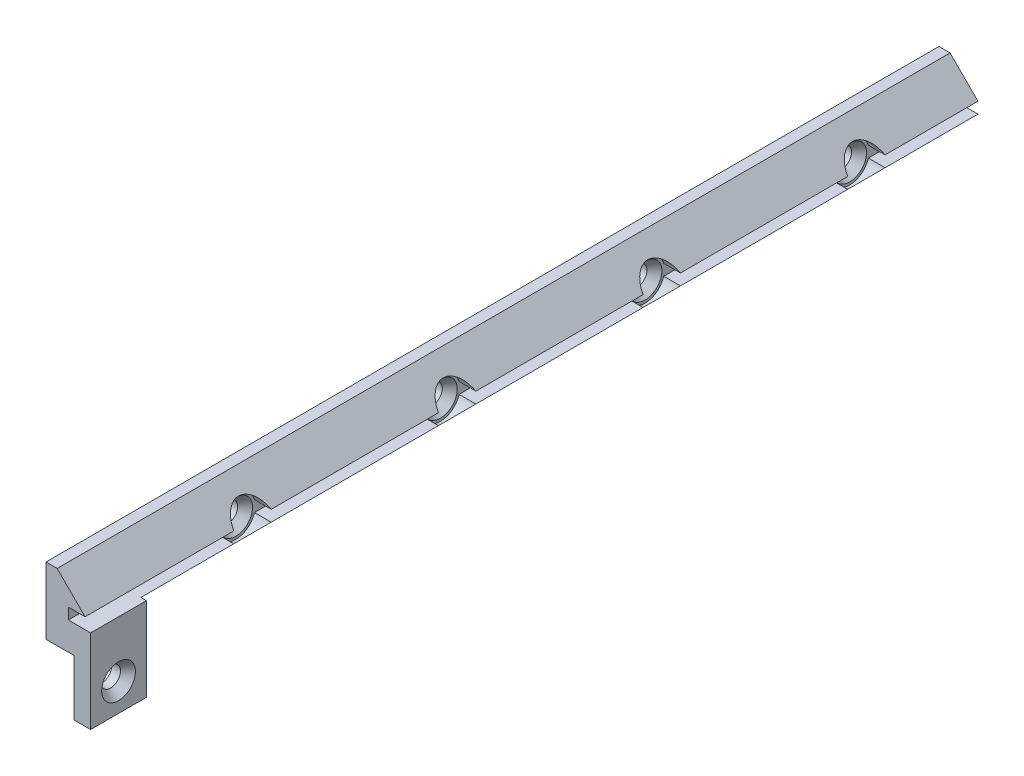
SolidWorks part; units mm, degrees
ref_plane "Front Plane" through (0, 0, 0) normal (0, 0, 1) x (1, 0, 0)
ref_plane "Top Plane" through (0, 0, 0) normal (0, 1, 0) x (1, 0, 0)
ref_plane "Right Plane" through (0, 0, 0) normal (1, 0, 0) x (0, 0, -1)
sketch "Sketch1" plane through (0, 0, 0) normal (0, 0, 1) x (1, 0, 0)
  line L0 (-2, 0) -> (0, 0) construction
  line L1 (-2, -3) -> (2, -3)
  line L2 (-2, -3) -> (-2, 3)
  line L3 (-2, 3) -> (2, 3)
  line L4 (2, -3) -> (2, -0.5)
  line L5 (-2, -3) -> (2, 3) construction
  line L6 (-2, 3) -> (2, -3) construction
  line L7 (2, 0.5) -> (0, 0.5)
  line L9 (2, -0.5) -> (0, -0.5)
  line L10 (0, 0.5) -> (0, -0.5)
  line L11 (2, 0.5) -> (2, 3)
  point P0 (0, 0)
  dimension "D1" = 1
  dimension "D2" = 6
  dimension "D3" = 2
  dimension "D4" = 4
extrude "Boss-Extrude1" add sketch "Sketch1" along normal blind 75
sketch "Sketch5" plane through (2, 0, 0) normal (1, 0, 0) x (0, 0, -1)
  line L1 (-75, 0) -> (0, 0) construction
  line L4 (-75, -0.5) -> (-75, 0.5) construction
  circle A0 centre (-65, 0) radius 1.75
  circle A1 centre (-46.6667, 0) radius 1.75
  circle A2 centre (-28.3333, 0) radius 1.75
  circle A3 centre (-10, 0) radius 1.75
  point P6 (-65, 0)
  dimension "D1" = 3.5
  dimension "D2" = 10
  dimension "D3" = 10
  dimension "D5" = 4
extrude "Cut-Extrude1" cut sketch "Sketch5" against normal up to surface (2 mm away) up to face at (0, 0, 37.5)
hole_wizard "CSK for #0 Flat Head Machine Screw2" positions "Sketch4" profile "Sketch2" countersink size "#0" standard "ANSI Inch"
sketch "Sketch4" plane through (0, 0, 0) normal (1, 0, 0) x (0, 0, -1)
  arc A0 (-63.3229, 0.5) -> (-66.6771, 0.5) centre (-65, 0) ccw construction
  arc A3 (-44.9896, 0.5) -> (-48.3437, 0.5) centre (-46.6667, 0) ccw construction
  arc A4 (-8.323, 0.5) -> (-11.6771, 0.5) centre (-10, 0) ccw construction
  point P0 (-65, 0)
  point P2 (-10, 0)
  point P4 (-46.6667, 0)
  point P25 (-28.3333, 0)
sketch "Sketch2" plane through (0, 0, 65) normal (0, 1, 0) x (0, 0, -1)
  line L0 (0, 0) -> (0, 3.8362)
  line L1 (0, 3.8362) -> (0.889, 3.302)
  line L2 (0.889, 3.302) -> (0.889, 0.7159)
  line L3 (0.889, 0.7159) -> (1.5113, 0)
  line L5 (1.5113, 0) -> (0, 0)
  line L6 (-0.889, 0.7159) -> (-1.5113, 0) construction
  line L10 (0, 3.8362) -> (-0.889, 3.302) construction
  line L11 (0, -6.35) -> (0, 107.95) construction
  dimension "Hole Dia." = 1.778
  dimension "Hole Depth" = 3.302
  dimension "Near C'Sink Dia." = 3.0226
  dimension "Near C'Sink Angle" = 82
  dimension "Drill Angle" = 118
chamfer "Chamfer1" distance 3 angle 45 2 edges at (2, -3, 37.5) (2, 3, 37.5)
sketch "Sketch6" plane through (0, 0, 75) normal (0, 0, 1) x (1, 0, 0)
  line L0 (-2, -3) -> (-1, -3) construction
  line L1 (2, 3) -> (2, 0.5)
  line L2 (-2, 3) -> (-2, -3)
  line L3 (-2, -3) -> (2, -3)
  line L5 (-2, 3) -> (-2, -3) construction
  line L6 (2, -0.5) -> (2, -3)
  line L7 (2, 0.5) -> (0, 0.5)
  line L8 (0, 0.5) -> (1.5, 0.5) construction
  line L9 (2, -0.5) -> (0, -0.5)
  line L10 (0, 0.5) -> (0, -0.5)
  line L11 (-2, 3) -> (2, 3)
  line L12 (-1, 3) -> (-2, 3) construction
  line L13 (2, -3) -> (0.5, -3)
  line L14 (2, -3) -> (2, -8)
  line L15 (2, -8) -> (0.5, -8)
  line L16 (0.5, -3) -> (0.5, -8)
  line M4 (-2, -3) -> (-1, -3)
  line M6 (1.5, -0.5) -> (0, -0.5)
  line M7 (0, -0.5) -> (0, 0.5)
  line M8 (0, 0.5) -> (1.5, 0.5)
  line M10 (-1, 3) -> (-2, 3)
  line M11 (-2, 3) -> (-2, -3)
  line M21 (-1, -3) -> (1.5, -0.5)
  line M22 (1.5, 0.5) -> (-1, 3)
  dimension "D1" = 4
  dimension "D2" = 2.5
  dimension "D3" = 5
  dimension "D4" = 1.5
extrude "Boss-Extrude2" add sketch "Sketch6" along normal blind 5 contours M11 M4 M21 M6 M7 M8 M22 M10 | L6 L9 L3 M21 | L3 L16 L15 L14 region at (-0.7956, 0, 75) region at (0.9762, -2.0476, 75) region at (1.25, -5.5, 75)
hole_wizard "CSK for #0 Flat Head Machine Screw1" positions "Sketch8" profile "Sketch7" countersink size "#0" standard "ANSI Inch"
sketch "Sketch8" plane through (2, 0, 0) normal (1, 0, 0) x (0, 0, -1)
  line L1 (-80, -8) -> (-75, -8) construction
  line L2 (-80, -8) -> (-80, -3) construction
  line L3 (-80, -3) -> (-75, -3) construction
  line L4 (-75, -8) -> (-75, -3) construction
  line L5 (-80, -8) -> (-75, -3) construction
  line L6 (-80, -3) -> (-75, -8) construction
  line L8 (-80, -0.5) -> (-80, -8) construction
  line L9 (-80, -8) -> (-75, -8) construction
  point P0 (-77.5, -5.5)
  point P4 (-77.5, -5.5)
  dimension "D1" = 5
sketch "Sketch7" plane through (2, -5.5, 77.5) normal (0, 1, 0) x (0, 0, -1)
  line L0 (0, 0) -> (0, 3.8362)
  line L1 (0, 3.8362) -> (0.889, 3.302)
  line L2 (0.889, 3.302) -> (0.889, 0.7159)
  line L3 (0.889, 0.7159) -> (1.5113, 0)
  line L5 (1.5113, 0) -> (0, 0)
  line L6 (-0.889, 0.7159) -> (-1.5113, 0) construction
  line L10 (0, 3.8362) -> (-0.889, 3.302) construction
  line L11 (0, -6.35) -> (0, 107.95) construction
  dimension "Hole Dia." = 1.778
  dimension "Hole Depth" = 3.302
  dimension "Near C'Sink Dia." = 3.0226
  dimension "Near C'Sink Angle" = 82
  dimension "Drill Angle" = 118
